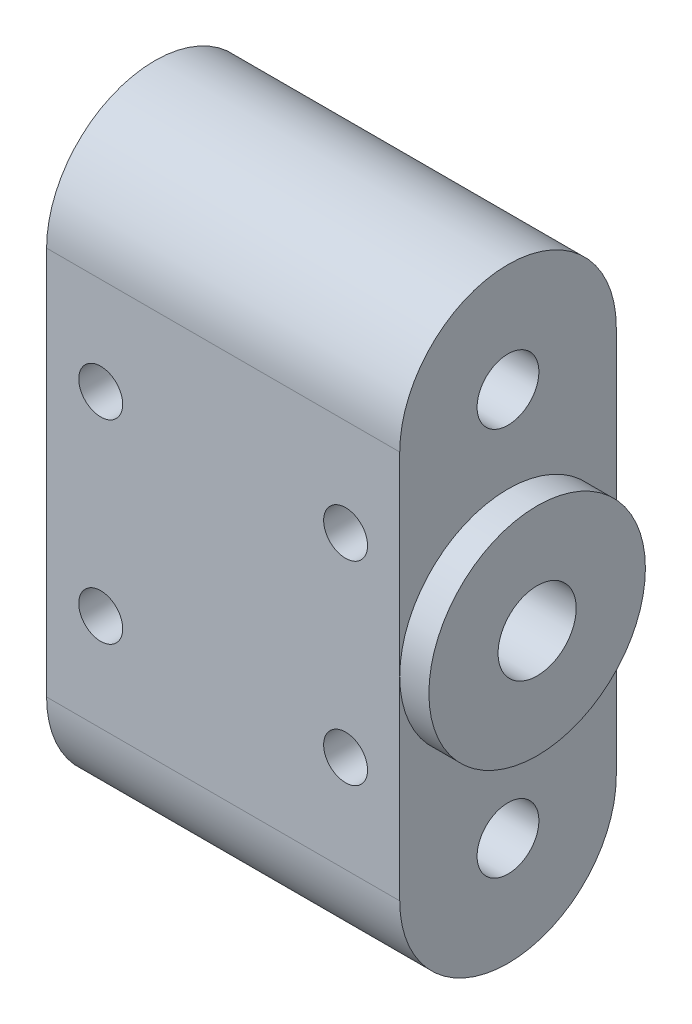
SolidWorks part; units mm, degrees
material "PET"
ref_plane "Front" through (0, 0, 0) normal (0, 0, 1) x (1, 0, 0)
ref_plane "Top" through (0, 0, 0) normal (0, 1, 0) x (1, 0, 0)
ref_plane "Right" through (0, 0, 0) normal (1, 0, 0) x (0, 0, -1)
sketch "Sketch1" plane through (0, 0, 0) normal (1, 0, 0) x (0, 0, -1)
  line L0 (0, 12.7) -> (0, -12.7) construction
  line L1 (7.0739, 12.7) -> (7.0739, -12.7)
  line L2 (-7.0739, 12.7) -> (-7.0739, -12.7)
  arc A0 (7.0739, 12.7) -> (-7.0739, 12.7) centre (0, 12.7) ccw
  arc A1 (-7.0739, -12.7) -> (7.0739, -12.7) centre (0, -12.7) ccw
  point P2 (0, 0)
  dimension "D1" = 14.1478
  dimension "D2" = 25.4
extrude "Boss-Extrude1" add sketch "Sketch1" along normal blind 23.075
sketch "Sketch8" plane through (23.075, 0, 0) normal (1, 0, 0) x (0, 0, -1)
  circle A0 centre (0, 0) radius 7.0739
  dimension "D1" = 14.1478
extrude "Boss-Extrude2" add sketch "Sketch8" along normal blind 1.905
hole_wizard "1/4-20 Tapped Hole1" positions "Sketch9" profile "Sketch10" tap size "1/4-20" standard "ANSI Inch" end condition through all
sketch "Sketch9" plane through (24.98, 0, 0) normal (1, 0, 0) x (0, 0, -1)
  point P0 (0, 0)
sketch "Sketch10" plane through (24.98, 0, 0) normal (0, 1, 0) x (0, 0, -1)
  line L0 (0, 0) -> (0, 24.98)
  line L1 (0, 24.98) -> (2.5527, 24.98)
  line L2 (2.5527, 24.98) -> (2.5527, 0)
  line L5 (2.5527, 0) -> (0, 0)
  line L11 (0, -6.35) -> (0, 107.95) construction
  dimension "Thru Tap Drill Dia." = 5.1054
  dimension "Thru Tap Drill Depth" = 24.98
cosmetic thread "Hole Thread8" parameters "D2"=6.35
hole_wizard "#10-32 Tapped Hole1" positions "Sketch4" profile "Sketch5" tap size "#10-32" standard "ANSI Inch" end condition through all
sketch "Sketch4" plane through (23.075, 0, 0) normal (1, 0, 0) x (0, 0, -1)
  point P0 (0, 12.7)
  point P2 (0, -12.7)
sketch "Sketch5" plane through (23.075, 12.7, 0) normal (0, 1, 0) x (0, 0, -1)
  line L0 (0, 0) -> (0, 23.075)
  line L1 (0, 23.075) -> (2.0193, 23.075)
  line L2 (2.0193, 23.075) -> (2.0193, 0)
  line L5 (2.0193, 0) -> (0, 0)
  line L11 (0, -6.35) -> (0, 107.95) construction
  dimension "Thru Tap Drill Dia." = 4.0386
  dimension "Thru Tap Drill Depth" = 23.075
cosmetic thread "Hole Thread2" parameters "D2"=4.826
cosmetic thread "Hole Thread3" parameters "D2"=4.826
hole_wizard "#6-40 Tapped Hole1" positions "Sketch6" profile "Sketch7" tap size "#6-40" standard "ANSI Inch" end condition through all
sketch "Sketch6" plane through (0, 0, 7.0739) normal (0, 0, 1) x (1, 0, 0)
  line L5 (3.5375, 6.35) -> (3.5375, -6.35) construction
  line L7 (0, 0) -> (23.075, 0) construction
  line L8 (0, 12.7) -> (0, -12.7) construction
  line L12 (3.5375, 6.35) -> (19.5375, 6.35) construction
  line L14 (11.5375, 6.35) -> (11.5375, 0) construction
  line L15 (23.075, 12.7) -> (23.075, 0) construction
  point P0 (3.5375, 6.35)
  point P2 (19.5375, 6.35)
  point P4 (3.5375, -6.35)
  point P6 (19.5375, -6.35)
  point P54 (3.5375, 0)
  dimension "D1" = 16
  dimension "D2" = 12.7
cosmetic thread "Hole Thread4" parameters "D2"=3.5052
cosmetic thread "Hole Thread5" parameters "D2"=3.5052
cosmetic thread "Hole Thread6" parameters "D2"=3.5052
cosmetic thread "Hole Thread7" parameters "D2"=3.5052
sketch "Sketch7" plane through (3.5375, 6.35, 7.0739) normal (1, 0, 0) x (0, -1, 0)
  line L0 (0, 0) -> (0, 14.1478)
  line L1 (0, 14.1478) -> (1.4351, 14.1478)
  line L2 (1.4351, 14.1478) -> (1.4351, 0)
  line L5 (1.4351, 0) -> (0, 0)
  line L11 (0, -6.35) -> (0, 107.95) construction
  dimension "Thru Tap Drill Dia." = 2.8702
  dimension "Thru Tap Drill Depth" = 14.1478
